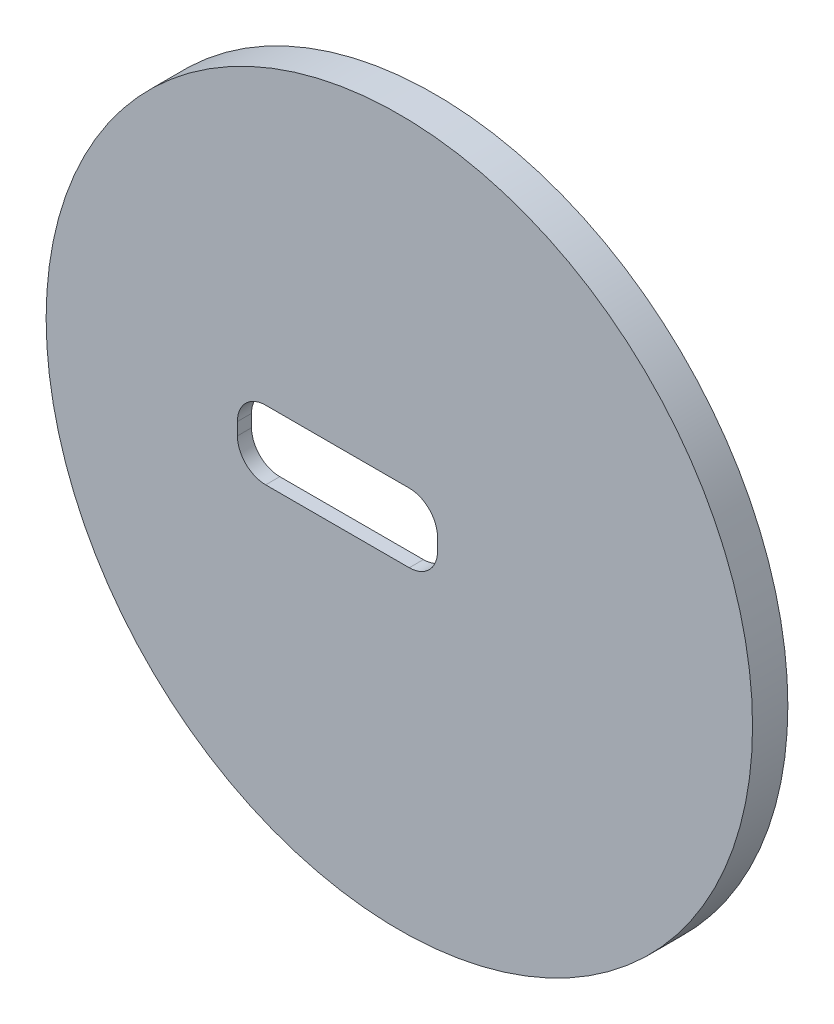
SolidWorks part; units mm, degrees
ref_plane "Front Plane" through (0, 0, 0) normal (0, 0, 1) x (1, 0, 0)
ref_plane "Top Plane" through (0, 0, 0) normal (0, 1, 0) x (1, 0, 0)
ref_plane "Right Plane" through (0, 0, 0) normal (1, 0, 0) x (0, 0, -1)
sketch "Sketch2" plane through (0, 0, 0) normal (0, 0, 1) x (1, 0, 0)
  line L1 (-34.62, 13.335) -> (12.37, 13.335)
  line L2 (-34.62, 13.335) -> (-34.62, -13.335)
  line L3 (-34.62, -13.335) -> (12.37, -13.335)
  line L4 (12.37, 13.335) -> (12.37, -13.335)
  line L5 (-34.62, 13.335) -> (12.37, -13.335) construction
  line L6 (-34.62, -13.335) -> (12.37, 13.335) construction
  line L11 (-27.0328, 5.4821) -> (6.8604, -6.1981) construction
  line L12 (-30.937, -10.386) -> (12.0283, 12.1376) construction
  circle A1 centre (0, 0) radius 3
  point P1 (-11.125, 0)
  point P4 (-11.125, 0)
  dimension "D1" = 12.37
  dimension "D2" = 6
  dimension "D6" = 39.624
  dimension "D5" = 13.335
  dimension "D3" = 46.99
  dimension "D4" = 26.67
sketch "Sketch3" plane through (0, 0, 0) normal (0, 0, 1) x (1, 0, 0)
  line L1 (-41.3384, 18.8331) -> (19.0884, 18.8331)
  line L2 (-41.3384, 18.8331) -> (-41.3384, -18.8331)
  line L3 (-41.3384, -18.8331) -> (19.0884, -18.8331)
  line L4 (19.0884, 18.8331) -> (19.0884, -18.8331)
  line L5 (-41.3384, 18.8331) -> (19.0884, -18.8331) construction
  line L6 (-41.3384, -18.8331) -> (19.0884, 18.8331) construction
  circle A0 centre (0, 0) radius 63.5
  circle A1 centre (0, 0) radius 57.15
  point P4 (-11.125, 0)
  dimension "D1" = 127
  dimension "D2" = 114.3
extrude "Boss-Extrude1" add sketch "Sketch3" along normal blind 6.35 contours A1 | A0 A1 | L2 L1 L4 L3 region at (-61.7039, 0, 0) region at (-55.5336, 0, 0)
extrude "Cut-Extrude1" cut sketch "Sketch2" along normal blind 3.81 contours L4 L1 L2 L3 A1 | A1 | A1 region at (-11.3818, 0, 0) region at (0, 0, 0)
fillet "Fillet1" radius 6.35 4 edges at (-34.62, 13.335, 1.905) (12.37, 13.335, 1.905) (-34.62, -13.335, 1.905) (12.37, -13.335, 1.905)
sketch "Sketch6" plane through (0, 0, 0) normal (0, 0, 1) x (1, 0, 0)
  line L1 (-29.1104, 6.1981) -> (6.8604, 6.1981)
  line L2 (-29.1104, 6.1981) -> (-29.1104, -6.1981)
  line L3 (-29.1104, -6.1981) -> (6.8604, -6.1981)
  line L4 (6.8604, 6.1981) -> (6.8604, -6.1981)
  line L5 (-29.1104, 6.1981) -> (6.8604, -6.1981) construction
  line L6 (-29.1104, -6.1981) -> (6.8604, 6.1981) construction
  point P0 (-11.125, 0)
extrude "Cut-Extrude2" cut sketch "Sketch6" along normal blind 6.35
fillet "Fillet2" radius 5.08 4 edges at (-29.1104, -6.1981, 5.08) (-29.1104, 6.1981, 5.08) (6.8604, 6.1981, 5.08) (6.8604, -6.1981, 5.08)
extrude "Cut-Extrude4" cut sketch "Sketch3<4>" along normal blind 3.81 contours A1 L1 L4 L3 L2 region at (-55.5336, 0, 0)
sketch "Sketch3<4>" plane through (0, 0, 0) normal (0, 0, 1) x (1, 0, 0) same geometry as "Sketch3"
fillet "Fillet3" radius 5.08 4 edges at (19.0884, -18.8331, 1.905) (19.0884, 18.8331, 1.905) (-41.3384, -18.8331, 1.905) (-41.3384, 18.8331, 1.905)
